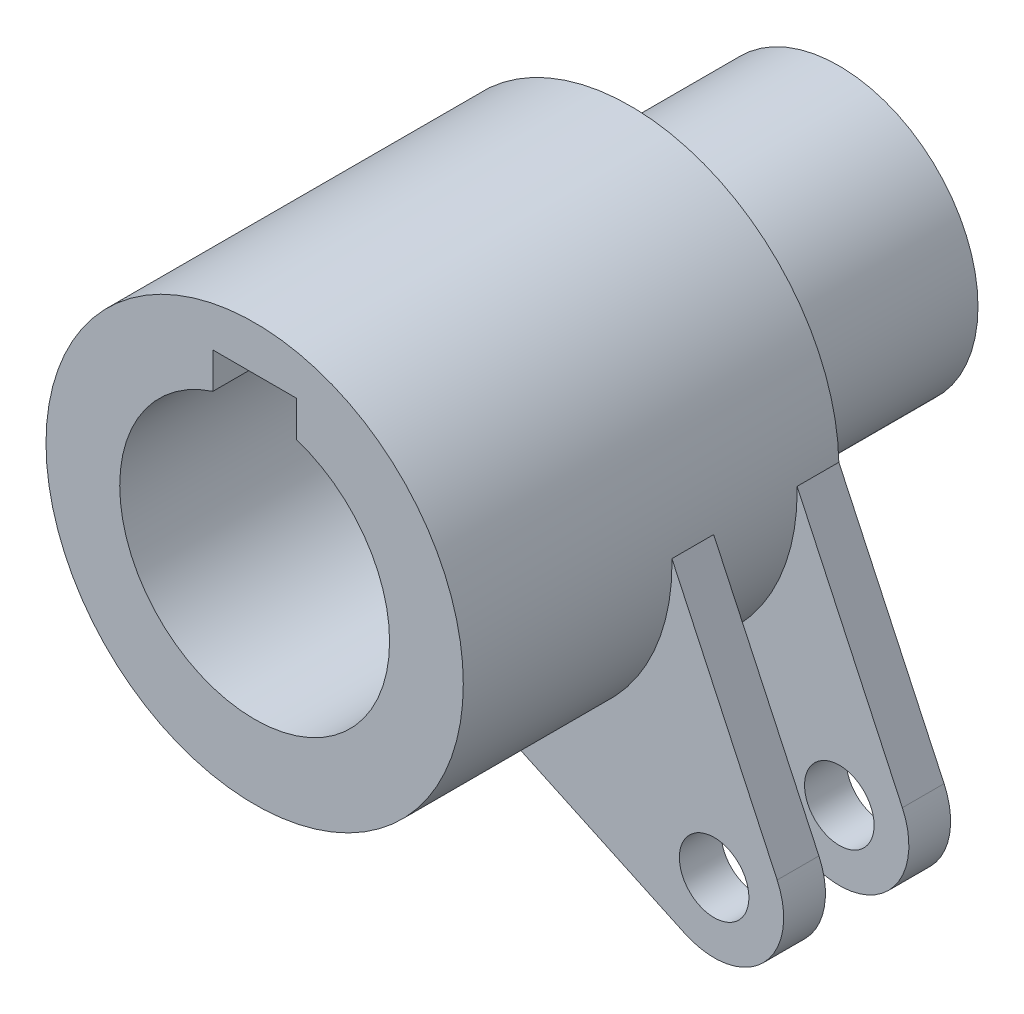
SolidWorks part; units mm, degrees
ref_plane "Front Plane" through (0, 0, 0) normal (0, 0, 1) x (1, 0, 0)
ref_plane "Top Plane" through (0, 0, 0) normal (0, 1, 0) x (1, 0, 0)
ref_plane "Right Plane" through (0, 0, 0) normal (1, 0, 0) x (0, 0, -1)
sketch "Sketch2" plane through (0, 0, 0) normal (0, 0, 1) x (1, 0, 0)
  line L0 (0, 0) -> (0, 32.7887) construction
  line L1 (-2.5301, 23.1109) -> (2.5301, 23.1109) construction
  line L2 (0, 0) -> (2.5301, 23.1109) construction
  line L3 (0, 0) -> (10.2819, 20.8518) construction
  line L5 (-2, 3.1) -> (2, 3.1)
  line L6 (-2, 3.1) -> (-2, 5.1)
  line L7 (-2, 5.1) -> (2, 5.1)
  line L8 (2, 3.1) -> (2, 5.1)
  line L9 (-2, 3.1) -> (2, 5.1) construction
  line L10 (-2, 5.1) -> (2, 3.1) construction
  arc A0 (0.752, 29.9906) -> (-0.752, 29.9906) centre (0, 0) ccw
  circle A1 centre (0, 0) radius 23.249
  circle A2 centre (0, 0) radius 10
  circle A3 centre (0, 0) radius 4.1
  arc A4 (10.964, 27.9247) -> (9.5508, 28.4391) centre (0, 0) ccw
  arc A5 (10.2819, 20.8518) -> (10.964, 27.9247) centre (0.4712, 25.3673) ccw
  arc A6 (-0.752, 29.9906) -> (-2.5301, 23.1109) centre (8.2334, 23.9986) ccw
  arc A7 (2.5301, 23.1109) -> (0.752, 29.9906) centre (-8.2334, 23.9986) ccw
  circle A8 centre (0, 0) radius 25.3717 construction
  arc A9 (9.5508, 28.4391) -> (5.5269, 22.5825) centre (15.9449, 19.7353) ccw
  arc A10 (19.8536, 22.4908) -> (18.7015, 23.4575) centre (0, 0) ccw
  arc A11 (16.7936, 16.0777) -> (19.8536, 22.4908) centre (9.1189, 23.6763) ccw
  arc A12 (18.7015, 23.4575) -> (12.9173, 19.3303) centre (21.7332, 13.0917) ccw
  point P2 (0, 4.1)
  point P19 (0, 23.1109)
  dimension "D1" = 60
  dimension "D2" = 46.498
  dimension "D3" = 20
  dimension "D4" = 10.8
  dimension "D5" = 10.8
  dimension "D7" = 50.7434
  dimension "D8" = 1.5039
  dimension "D11" = 8.2
  dimension "D6" = 3
  dimension "D9" = 5.0601
  dimension "D10" = 20
  dimension "D12" = 4
  dimension "D13" = 2
sketch "Sketch3" plane through (0, 0, 0) normal (0, 0, 1) x (1, 0, 0)
  line L0 (0, 0) -> (18.0312, -18.0312) construction
  line L1 (0, 0) -> (42.1729, 0) construction
  line L2 (22.5628, -15.9181) -> (14.9969, 0.307)
  line L3 (15.9181, -22.5628) -> (-0.307, -14.9969)
  line L4 (-2, 3.1) -> (2, 3.1) construction
  line L5 (2, 3.1) -> (2, 5.1) construction
  line L6 (-2, 5.1) -> (2, 5.1) construction
  line L7 (-2, 3.1) -> (-2, 5.1) construction
  line L8 (-2, 3.1) -> (2, 3.1)
  line L9 (2, 3.1) -> (2, 5.1)
  line L10 (-2, 5.1) -> (2, 5.1)
  line L11 (-2, 3.1) -> (-2, 5.1)
  circle A0 centre (0, 0) radius 15
  circle A1 centre (18.0312, -18.0312) radius 2.5
  circle A2 centre (18.0312, -18.0312) radius 5
  circle A3 centre (0, 0) radius 30.5 construction
  circle A4 centre (0, 0) radius 4.1 construction
  circle A5 centre (0, 0) radius 4.1
  dimension "D1" = 30
  dimension "D3" = 10
  dimension "D4" = 5
  dimension "D5" = 61
  dimension "D2" = 45
  dimension "D6" = 20
  dimension "D7" = 20
extrude "Boss-Extrude4" add sketch "Sketch3" against normal blind 12 separate body contours A0 region at (14.575, 0.1492, 0)
extrude "Boss-Extrude5" add sketch "Sketch3<4>" against normal blind 3 from surface contours A2 L2 A0 L3 | A2 A1 region at (12.5423, -12.5423, 0) region at (22.7746, -16.9796, 0) starting at face at (0, 2.4198, 0)
sketch "Sketch3<4>" plane through (0, 0, 0) normal (0, 0, 1) x (1, 0, 0) same geometry as "Sketch3"
extrude "Boss-Extrude6" add sketch "Sketch3<5>" along normal blind 3 from surface contours A2 L2 A0 L3 | A2 A1 region at (12.5423, -12.5423, 0) region at (22.7746, -16.9796, 0) starting at face at (0, 2.4198, -12)
sketch "Sketch3<5>" plane through (0, 0, 0) normal (0, 0, 1) x (1, 0, 0) same geometry as "Sketch3"
extrude "Boss-Extrude7" add sketch "Sketch2" against normal blind 15 from surface contours A2 A3 L6 L7 L8 region at (-9.7172, 0, 0) starting at face at (0, 2.4198, -12)
sketch "Sketch5" plane through (0, 0, 0) normal (0, 0, 1) x (1, 0, 0)
  line L1 (-3, 11.8) -> (3, 11.8)
  line L2 (-3, 11.8) -> (-3, 7.6)
  line L3 (-3, 7.6) -> (3, 7.6)
  line L4 (3, 11.8) -> (3, 7.6)
  line L5 (-3, 11.8) -> (3, 7.6) construction
  line L6 (-3, 7.6) -> (3, 11.8) construction
  circle A0 centre (0, 0) radius 9.7
  circle A1 centre (0, 0) radius 15
  circle A2 centre (0, 0) radius 15 construction
  point P6 (0, 9.7)
  dimension "D1" = 19.4
  dimension "D2" = 4.2
  dimension "D3" = 6
extrude "Boss-Extrude8" add sketch "Sketch5" along normal blind 15 contours A1 A0 L2 L1 L4 region at (-14.5757, 0, 0)
